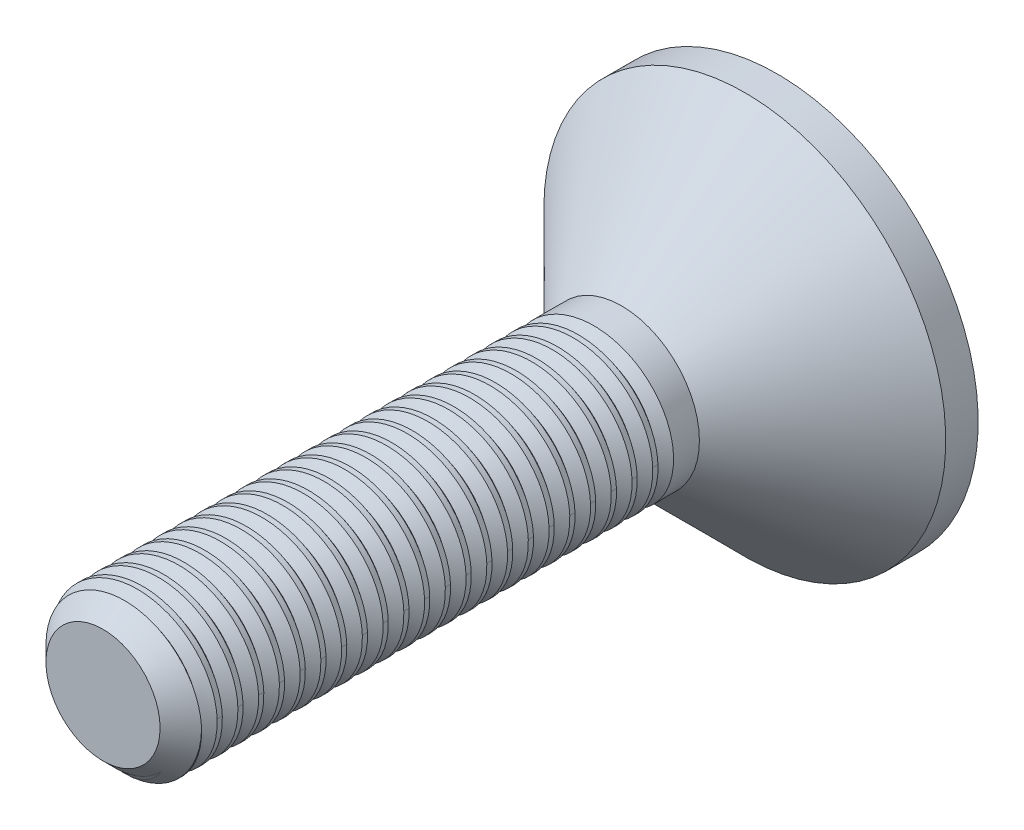
SolidWorks part; units mm, degrees
ref_plane "前视基准面" through (0, 0, 0) normal (0, 0, 1) x (1, 0, 0)
ref_plane "上视基准面" through (0, 0, 0) normal (0, 1, 0) x (1, 0, 0)
ref_plane "右视基准面" through (0, 0, 0) normal (1, 0, 0) x (0, 0, -1)
sketch "草图1" plane through (0, 0, 0) normal (0, 0, 1) x (1, 0, 0)
  circle A0 centre (0, 0) radius 8.65
  dimension "D1" = 17.3
extrude "凸台-拉伸1" add sketch "草图1" along normal blind 6
chamfer "倒角1" distance 5.65 angle 45 1 edges at (8.65, 0, 6)
sketch "草图3" plane through (0, 0, 6) normal (0, 0, 1) x (1, 0, 0)
  circle A1 centre (0, 0) radius 3
  circle A2 centre (0, 0) radius 3
  dimension "D1" = 0
extrude "凸台-拉伸2" add sketch "草图3" along normal blind 20
sketch "草图4" plane through (0, 0, 0) normal (0, 0, -1) x (-1, 0, 0)
  line L1 (1.4972, 3.1239) -> (-1.9568, 2.8585)
  line L2 (-1.9568, 2.8585) -> (-3.4539, -0.2654)
  line L3 (-3.4539, -0.2654) -> (-1.4972, -3.1239)
  line L4 (-1.4972, -3.1239) -> (1.9568, -2.8585)
  line L5 (1.9568, -2.8585) -> (3.4539, 0.2654)
  line L6 (3.4539, 0.2654) -> (1.4972, 3.1239)
  circle A0 centre (0, 0) radius 3 construction
  dimension "D1" = 6
extrude "切除-拉伸1" cut sketch "草图4" against normal blind 4
sketch "草图5" plane through (0, 0, 0) normal (0, 0, -1) x (-1, 0, 0)
  circle A0 centre (0, 0) radius 3.7567
extrude "切除-拉伸2" cut sketch "草图5" against normal blind 0.5
chamfer "倒角2" distance 0.8 angle 45 1 edges at (3, 0, 26)
sketch "草图6" plane through (0, 0, 26) normal (0, 0, 1) x (1, 0, 0)
  circle A0 centre (0, 0) radius 3
curve "螺旋线/涡状线1" pitch 0.8 height 19.2 radius 3 centre (0, 0, 26) axis (0, 0, -1) start towards (-0.7071, 0.7071, 0)
sketch "草图8" plane through (0, 0, 0) normal (1, 0, 0) x (0, 0, -1)
  line L0 (-25.6, 3) -> (-26.2, 3)
  line L1 (-26.2, 3) -> (-25.9, 2.6)
  line L2 (-25.9, 2.6) -> (-25.6, 3)
  line L3 (-25.9, 3) -> (-25.9, 2.6) construction
  dimension "D1" = 0.6
  dimension "D2" = 0.4
sweep "切除-扫描1" cut profiles "草图8" path "螺旋线/涡状线1"
sketch "草图9" plane through (0, 0, 0) normal (0, 0, -1) x (-1, 0, 0)
  circle A0 centre (0, 0) radius 7.75
  dimension "D1" = 15.5
extrude "切除-拉伸3" cut sketch "草图9" against normal through all flip side to cut
